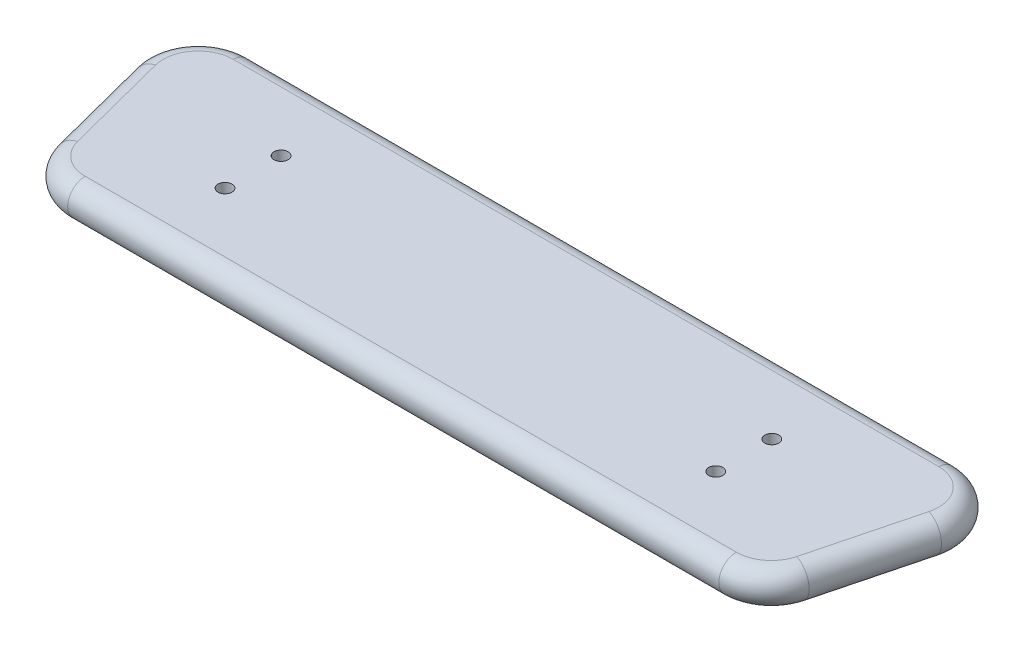
SolidWorks part; units mm, degrees
ref_plane "Front Plane" through (0, 0, 0) normal (0, 0, 1) x (1, 0, 0)
ref_plane "Top Plane" through (0, 0, 0) normal (0, 1, 0) x (1, 0, 0)
ref_plane "Right Plane" through (0, 0, 0) normal (1, 0, 0) x (0, 0, -1)
sketch "Sketch1" plane through (0, 0, 0) normal (0, 1, 0) x (1, 0, 0)
  line L0 (115.1494, 11.2443) -> (107.3909, -18.7557)
  line L1 (-100.6272, 30) -> (100.6272, 30)
  line L3 (-92.8687, -30) -> (92.8687, -30)
  line L7 (0, 0) -> (0, 19.7602) construction
  line L8 (-115.1494, 11.2443) -> (-107.3909, -18.7557)
  arc A0 (-107.3909, -18.7557) -> (-92.8687, -30) centre (-92.8687, -15) ccw
  arc A1 (107.3909, -18.7557) -> (92.8687, -30) centre (92.8687, -15) cw
  arc A2 (100.6272, 30) -> (115.1494, 11.2443) centre (100.6272, 15) cw
  arc A3 (-100.6272, 30) -> (-115.1494, 11.2443) centre (-100.6272, 15) ccw
  point P0 (0, 0)
  point P10 (-104.4829, -30)
  point P13 (104.4829, -30)
  point P16 (120, 30)
  point P19 (-120, 30)
  dimension "D2" = 15
  dimension "D1" = 240
  dimension "D3" = 75.5
extrude "Boss-Extrude1" add sketch "Sketch1" along normal blind 10 contours L1 A2 L0 A1 L3 A0 L8 A3
fillet "Fillet1" 2 edges at (0, 10, 30) (0, 0, 30) type full round first side face at (0, 10, 1.6082) second side face at (0, 0, 1.6082) middle face at (0, 5, 30)
sketch "Sketch3" plane through (0, 0, 0) normal (0, -1, 0) x (1, 0, 0)
  line L0 (0, 20.1575) -> (0, 0) construction
  line L1 (0, 0) -> (35.5947, 0) construction
  line L2 (92.8687, 30) -> (-92.8687, 30) construction
  circle A0 centre (-70, 8) radius 2
  circle A1 centre (-70, -8) radius 2
  circle A2 centre (70, -8) radius 2
  circle A3 centre (70, 8) radius 2
  dimension "D1" = 4
  dimension "D2" = 70
  dimension "D3" = 22
extrude "Cut-Extrude3" cut sketch "Sketch3" against normal blind 8 from offset 2 offset against normal yes
